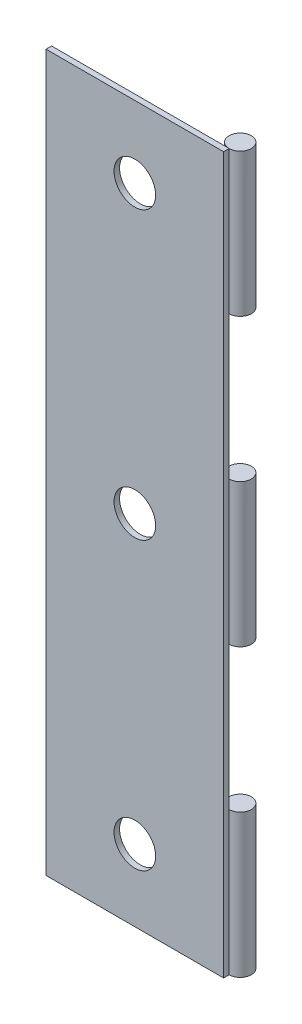
SolidWorks part; units mm, degrees
ref_plane "Front Plane" through (0, 0, 0) normal (0, 0, 1) x (1, 0, 0)
ref_plane "Top Plane" through (0, 0, 0) normal (0, 1, 0) x (1, 0, 0)
ref_plane "Right Plane" through (0, 0, 0) normal (1, 0, 0) x (0, 0, -1)
sketch "Sketch2" plane through (0, 0, 0) normal (0, 1, 0) x (1, 0, 0)
  circle A0 centre (0, 0) radius 1
extrude "Boss-Extrude1" add sketch "Sketch2" along normal blind 64.5
sketch "Sketch3" plane through (0, 0, 0) normal (0, 0, 1) x (1, 0, 0)
  line L0 (0, 64.5) -> (0, 51.6) construction
  line L1 (1, 64.5) -> (-1, 64.5) construction
  line L2 (0.0429, 38.7) -> (0.0429, 25.8) construction
  line L3 (-3.0046, 51.6) -> (3.0905, 51.6)
  line L4 (-3.0046, 51.6) -> (-3.0046, 38.7)
  line L5 (-3.0046, 38.7) -> (3.0905, 38.7)
  line L6 (3.0905, 51.6) -> (3.0905, 38.7)
  line L8 (-3.0046, 25.8) -> (3.0905, 25.8)
  line L9 (-3.0046, 25.8) -> (-3.0046, 12.9)
  line L10 (-3.0046, 12.9) -> (3.0905, 12.9)
  line L11 (3.0905, 25.8) -> (3.0905, 12.9)
  dimension "D1" = 12.9
  dimension "D2" = 12.9
extrude "Cut-Extrude1" cut sketch "Sketch3" against normal up to next and the other way up to next
sketch "Sketch4" plane through (0, 0, 0) normal (0, -1, 0) x (-1, 0, 0)
  line L1 (0, -1) -> (16, -1)
  line L2 (0, -1) -> (0, -1.5)
  line L3 (0, -1.5) -> (16, -1.5)
  line L4 (16, -1) -> (16, -1.5)
  circle A0 centre (0, 0) radius 1 construction
  dimension "D1" = 16
  dimension "D2" = 0.5
extrude "Boss-Extrude2" add sketch "Sketch4" against normal up to surface (64.5 mm away) up to face at (0, 64.5, 1)
sketch "Sketch5" plane through (0, 0, 1) normal (0, 0, -1) x (-1, 0, 0)
  line L0 (0, 0) -> (0, 12.9) construction
  line L1 (0, 64.5) -> (0, 0) construction
  line L2 (0, 6.45) -> (16, 6.45) construction
  line L3 (16, 64.5) -> (16, 0) construction
  line L4 (0, 32.25) -> (16, 32.25) construction
  line L5 (0, 51.5953) -> (0, 64.5) construction
  line L6 (0, 58.0477) -> (16, 58.0477) construction
  circle A0 centre (8, 32.25) radius 1.875
  circle A1 centre (8, 6.45) radius 1.875
  circle A2 centre (8, 58.0477) radius 1.875
  dimension "D1" = 3.75
extrude "Cut-Extrude2" cut sketch "Sketch5" against normal up to next (0.5 mm away)
